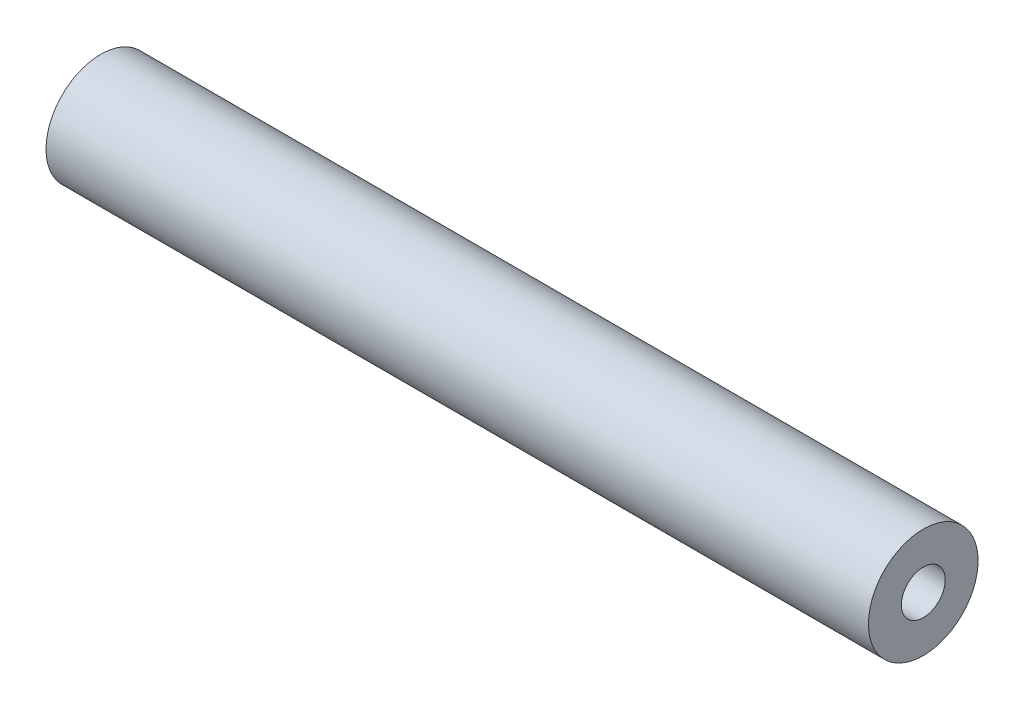
SolidWorks part; units mm, degrees
ref_plane "Front Plane" through (0, 0, 0) normal (0, 0, 1) x (1, 0, 0)
ref_plane "Top Plane" through (0, 0, 0) normal (0, 1, 0) x (1, 0, 0)
ref_plane "Right Plane" through (0, 0, 0) normal (1, 0, 0) x (0, 0, -1)
sketch "Sketch1" plane through (0, 0, 0) normal (0, 1, 0) x (1, 0, 0)
  line L0 (0, 0) -> (1.5582, 0) construction
  line L1 (0, 0.508) -> (19.05, 0.508)
  line L2 (0, 0.508) -> (0, 1.27)
  line L3 (0, 1.27) -> (19.05, 1.27)
  line L4 (19.05, 0.508) -> (19.05, 1.27)
  dimension "D1" = 2.54
  dimension "D2" = 1.016
  dimension "D3" = 19.05
revolve "Revolve1" add sketch "Sketch1" angle 360 about L0
